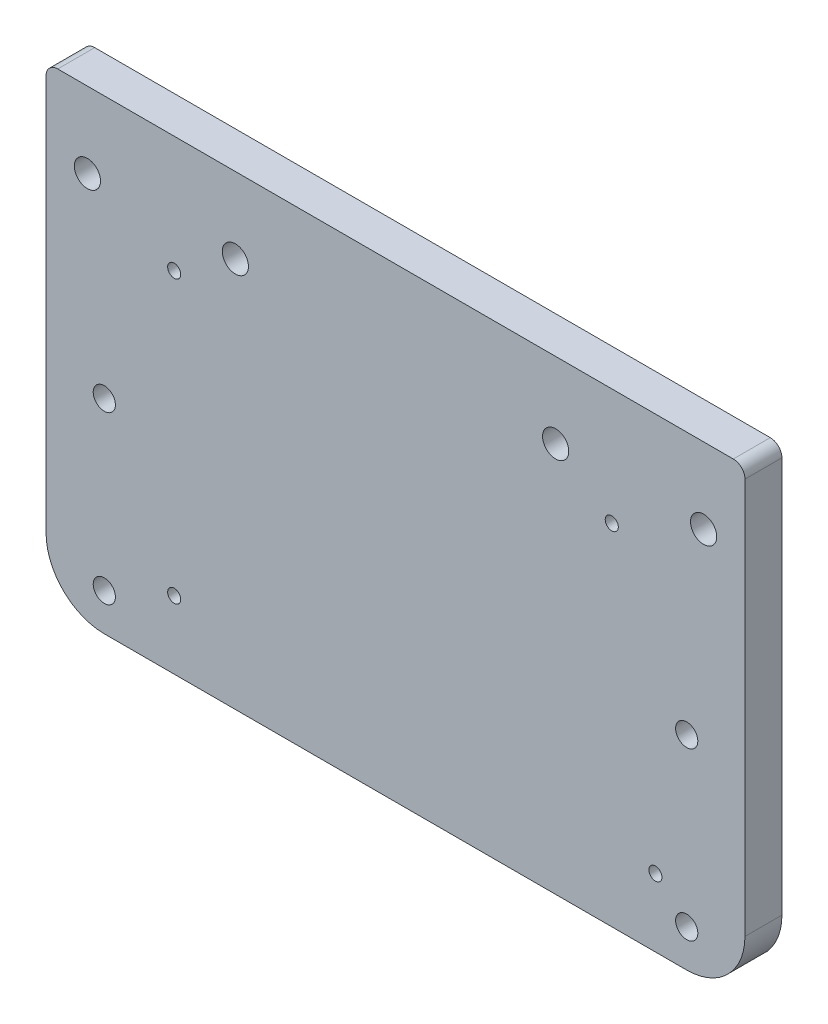
SolidWorks part; units mm, degrees
material "Cast Alloy Steel"
ref_plane "Front Plane" through (0, 0, 0) normal (0, 0, 1) x (1, 0, 0)
ref_plane "Top Plane" through (0, 0, 0) normal (0, 1, 0) x (1, 0, 0)
ref_plane "Right Plane" through (0, 0, 0) normal (1, 0, 0) x (0, 0, -1)
sketch "Sketch1" plane through (0, 0, 0) normal (0, 0, 1) x (1, 0, 0)
  line L0 (60, 0) -> (-60, 0)
  line L1 (-60, 0) -> (-60, -80)
  line L2 (-60, -80) -> (60, -80)
  line L3 (0, 0) -> (0, -80) construction
  line L4 (60, 0) -> (60, -80)
  dimension "D1" = 80
  dimension "D2" = 60
extrude "Boss-Extrude1" add sketch "Sketch1" along normal mid plane 6.35
fillet "Fillet1" radius 10 2 edges at (60, -80, 0) (-60, -80, 0)
sketch "Sketch2" plane through (0, 0, 3.175) normal (0, 0, 1) x (1, 0, 0)
  line L0 (60, 0) -> (-60, 0) construction
  line L1 (0, 0) -> (0, -17.0614) construction
  circle A0 centre (-52.9, -13) radius 2.25
  circle A1 centre (-27.5, -13) radius 2.25
  circle A2 centre (27.5, -13) radius 2.25
  circle A3 centre (52.9, -13) radius 2.25
  dimension "D1" = 4.5
  dimension "D2" = 25.4
  dimension "D3" = 13
  dimension "D4" = 27.5
extrude "Cut-Extrude1" cut sketch "Sketch2" against normal through all
ref_plane "Plane1" through (60, -70, 3.175) normal (0, 1, 0) x (1, 0, 0)
sketch "Sketch6" plane through (60, 0, 0) normal (1, 0, 0) x (0, 0, -1)
  line L0 (3.175, -63.9715) -> (20.175, -63.9715)
  line L2 (20.175, -63.9715) -> (20.175, -54.4715)
  line L3 (20.175, -54.4715) -> (3.175, -54.4715)
  line L4 (3.175, -54.4715) -> (3.175, -63.9715)
  line L5 (3.175, -70) -> (3.175, 0) construction
  circle A0 centre (15.175, -59.3208) radius 3
  dimension "D1" = 6
  dimension "D2" = 12
  dimension "D3" = 17
  dimension "D4" = 9.5
extrude "Boss-Extrude3" [suppressed] add sketch "Sketch6" against normal blind 30
fillet "Fillet3" [suppressed] radius 3
mirror "Mirror1" [suppressed] about plane through (0, 0, 0) normal (1, 0, 0)
fillet "Fillet4" radius 2 2 edges at (-60, 0, 0) (60, 0, 0)
sketch "Sketch7" plane through (0, 0, 3.175) normal (0, 0, 1) x (1, 0, 0)
  line L0 (0, 0) -> (0, -26.8238) construction
  circle A0 centre (-50, -45) radius 1.905
  circle A1 centre (-50, -73.575) radius 1.905
  circle A2 centre (50, -73.575) radius 1.905
  circle A3 centre (50, -45) radius 1.905
  dimension "D1" = 3.81
  dimension "D2" = 28.575
  dimension "D3" = 50
  dimension "D4" = 45
extrude "Cut-Extrude2" cut sketch "Sketch7" against normal through all
sketch "Sketch8" plane through (0, 0, -3.175) normal (0, 0, -1) x (-1, 0, 0)
  line L0 (-37.133, -20) -> (38, -20) construction
  line L1 (-37.133, -20) -> (-44.626, -68.336) construction
  line L2 (-44.626, -68.336) -> (38, -68.336) construction
  line L3 (38, -68.336) -> (38, -20) construction
  circle A0 centre (-37.133, -20) radius 1.125
  circle A1 centre (38, -20) radius 1.125
  circle A2 centre (-44.626, -68.336) radius 1.125
  circle A3 centre (38, -68.336) radius 1.125
  dimension "D5" = 2.25
  dimension "D1" = 82.626
  dimension "D2" = 48.336
  dimension "D3" = 75.133
  dimension "D4" = 20
  dimension "D6" = 38
extrude "Cut-Extrude3" cut sketch "Sketch8" against normal through all
